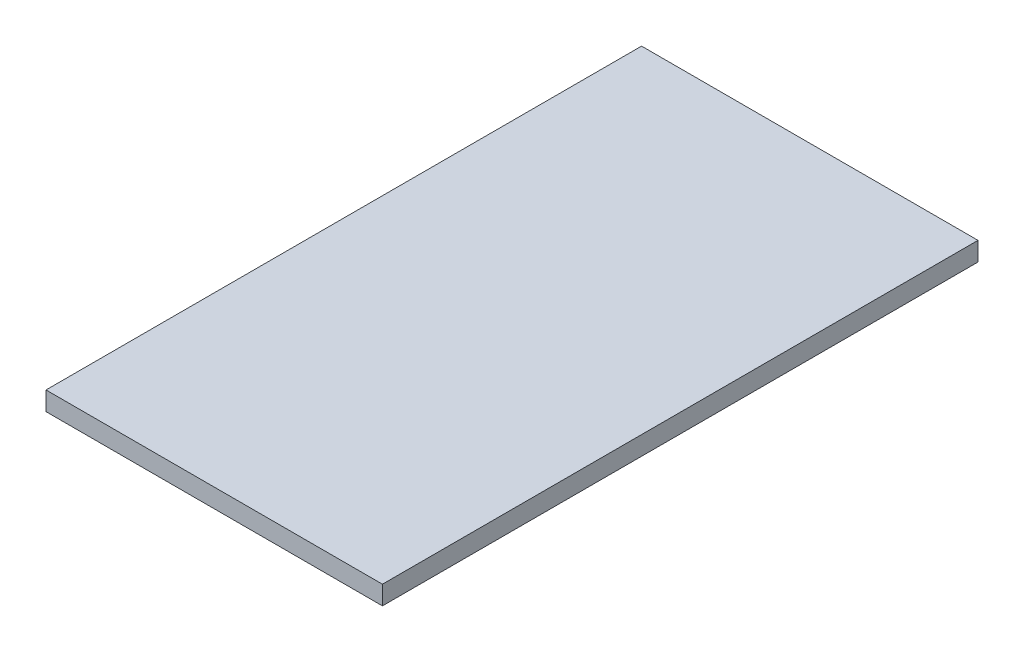
SolidWorks part; units mm, degrees
material "Perspex (TM) GS Acrylic Cast Sheet"
ref_plane "Front Plane" through (0, 0, 0) normal (0, 0, 1) x (1, 0, 0)
ref_plane "Top Plane" through (0, 0, 0) normal (0, 1, 0) x (1, 0, 0)
ref_plane "Right Plane" through (0, 0, 0) normal (1, 0, 0) x (0, 0, -1)
sketch "Sketch1" plane through (0, 0, 0) normal (0, 1, 0) x (1, 0, 0)
  line L1 (-80.5, -142.5) -> (80.5, -142.5)
  line L2 (-80.5, -142.5) -> (-80.5, 142.5)
  line L3 (-80.5, 142.5) -> (80.5, 142.5)
  line L4 (80.5, -142.5) -> (80.5, 142.5)
  line L5 (-80.5, -142.5) -> (80.5, 142.5) construction
  line L6 (-80.5, 142.5) -> (80.5, -142.5) construction
  point P0 (0, 0)
  dimension "D2" = 285
  dimension "D1" = 161
extrude "Boss-Extrude1" add sketch "Sketch1" along normal blind 9
equation "\"PCLength\"= 143mm'Length across I/O from PS to GPU"
equation "\"PCWidth\"= 340mm'Distance of longest part parallel to GPU(ussually GPU)"
equation "\"PCHeight\"= 190mm'Tallest point with mobo laying flat"
equation "\"WallThickness\"= 9mm'Thickness of each outer tank wall"
equation "\"ThermoBarrierThickness\"= 6mm'Thickness of barrier between hot side and cold side"
equation "\"HotSideGap\"= 15mm'Space in the hot side that hot fluid flows into"
equation "\"PCClearance\"= 40mm'Clearance from top of tank to top of PC"
equation "\"RadiatorHeight\"= 277.37mm'Final Height from ground of radiators"
equation "\"D2@Sketch1\"=\"PCHeight\" + \"ThermoBarrierThickness\" + \"HotSideGap\" + (2 * \"WallThickness\") + \"AirflowGap\" + 30"
equation "\"D1@Boss-Extrude1\"=\"WallThickness\""
equation "\"D1@Sketch1\"=\"PCLength\" + (2 * \"WallThickness\")"
equation "\"AirflowGap\"= 26mm'Distance between radiators and tank for airflow"
equation "\"VolumeSubtraction\"= 230mm"
